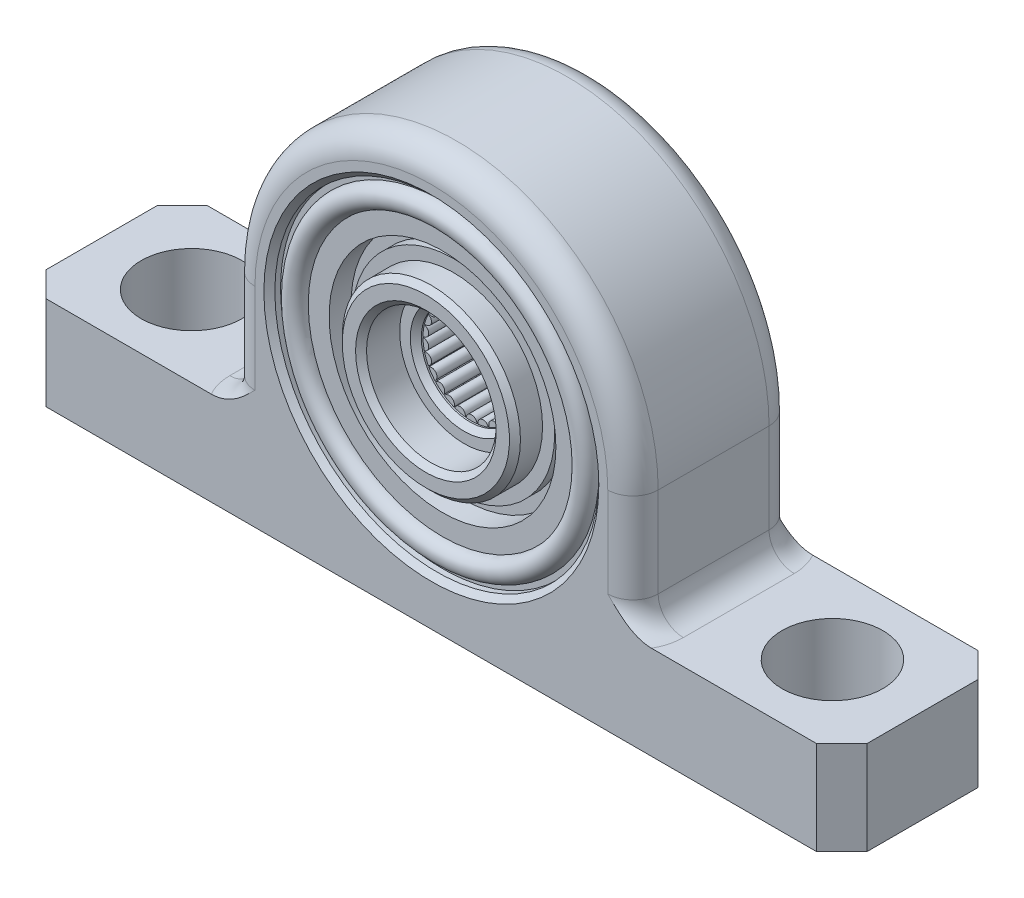
SolidWorks part; units mm, degrees
ref_plane "Front Plane" through (0, 0, 0) normal (0, 0, 1) x (1, 0, 0)
ref_plane "Top Plane" through (0, 0, 0) normal (0, 1, 0) x (1, 0, 0)
ref_plane "Right Plane" through (0, 0, 0) normal (1, 0, 0) x (0, 0, -1)
sketch "Sketch1" plane through (0, 0, 0) normal (0, 0, 1) x (1, 0, 0)
  line L0 (0, 14.25) -> (0, -14.25) construction
  line L1 (-28.5, -14.25) -> (28.5, -14.25) construction
  line L2 (-22.25, -14.25) -> (22.25, -14.25) construction
  line L3 (-28.5, -14.25) -> (-28.5, -7.75)
  line L4 (-28.5, -7.75) -> (-14, -7.75)
  line L5 (-14, 0.25) -> (-14, -7.75)
  line L6 (-15.75, -14.25) -> (-15.75, -7.75) construction
  circle A0 centre (-22.25, -14.25) radius 3.5
  circle A1 centre (22.25, -14.25) radius 3.5
  circle A2 centre (0, 0.25) radius 3
  circle A3 centre (0, 0.25) radius 14
  circle A4 centre (-22.25, -14.25) radius 6.5
  circle A5 centre (0, 0.25) radius 11.25
  circle A6 centre (0, 0.25) radius 4.5
  circle A7 centre (0, 0.25) radius 3.375 construction
  point P5 (0, -7.75)
  point P6 (0, 0.25)
  point P7 (-22.25, -14.25)
  point P8 (22.25, -14.25)
  point P22 (0, 3.25)
  point P23 (0, 11.5)
  point P25 (0, 9.5714)
  point P26 (0, 8.125)
  point P27 (0, 6.4375)
  point P28 (0, 4.75)
  dimension "Mounting Hole" = 7
  dimension "ID" = 6
  dimension "D4" = 9
  dimension "D9" = 6.75
  dimension "Height" = 28.5
  dimension "Length" = 57
  dimension "Lit G" = 6.5
  dimension "Center Height" = 14.5
  dimension "Mounting Center" = 44.5
  dimension "D1" = 1.75
  dimension "D2" = 11
  dimension "D3" = 8.25
  dimension "D5" = 6.75
  dimension "D6" = 1.9286
  dimension "D7" = 1.6875
  dimension "D8" = 1.6875
sketch "Sketch3" plane through (0, 0, 0) normal (0, 1, 0) x (1, 0, 0)
  line L0 (0, 5.6) -> (0, -5.6) construction
  point P2 (0, -6)
  point P4 (0, 4.5)
  dimension "CAD C" = 11.2
  dimension "Width" = 11.6
  dimension "D" = 10.5
sketch "Sketch6" plane through (0, 0, 0) normal (1, 0, 0) x (0, 0, -1)
  line L0 (-4.8262, 11.119) -> (-4.8262, 11.5)
  line L1 (-5.6, 11.5) -> (5.6, 11.5) construction
  line L2 (-5.6, 11.5) -> (-5.6, 0.25) construction
  line L3 (-5.6, 0.25) -> (5.6, 0.25) construction
  line L4 (5.6, 11.5) -> (5.6, 0.25) construction
  line L5 (-4.8262, 9.5714) -> (-4.8262, 8.125)
  line L6 (-3.3022, 8.125) -> (-4.8262, 8.125)
  line L7 (-4.0642, 7.2812) -> (-4.0642, 6.4375)
  line L8 (-4.0642, 6.4375) -> (-5.981, 6.4375)
  line L9 (-5.981, 6.4375) -> (-5.981, 4.75)
  line L10 (-4.0642, 7.2812) -> (-3.3022, 7.2812)
  line L11 (-3.3022, 7.2812) -> (-3.3022, 8.125)
  line L12 (-5.981, 4.75) -> (-3.3022, 4.75)
  line L13 (-3.3022, 4.75) -> (-3.3022, 3.25)
  line L14 (-3.3022, 3.25) -> (3.3022, 3.25)
  line L15 (-4.8262, 11.5) -> (4.8262, 11.5)
  line L16 (0, 0.25) -> (0, 32.5437) construction
  line L17 (0, 14.25) -> (0, -14.25) construction
  line L18 (0, 14.25) -> (0, -13.75) construction
  line L19 (3.3022, 4.75) -> (3.3022, 3.25)
  line L20 (5.981, 4.75) -> (3.3022, 4.75)
  line L21 (3.3022, 7.2812) -> (3.3022, 8.125)
  line L22 (4.0642, 7.2812) -> (3.3022, 7.2812)
  line L23 (5.981, 6.4375) -> (5.981, 4.75)
  line L24 (4.0642, 6.4375) -> (5.981, 6.4375)
  line L25 (4.0642, 7.2812) -> (4.0642, 6.4375)
  line L26 (3.3022, 8.125) -> (4.8262, 8.125)
  line L27 (4.8262, 9.5714) -> (4.8262, 8.125)
  line L28 (4.8262, 11.119) -> (4.8262, 11.5)
  arc A0 (-4.8262, 11.119) -> (-4.8262, 9.5714) centre (-4.8262, 10.3452) ccw
  arc A1 (4.8262, 11.119) -> (4.8262, 9.5714) centre (4.8262, 10.3452) cw
  point P40 (0, 11.5)
  point P41 (0, 3.25)
  dimension "D1" = 0.381
  dimension "D2" = 0.381
  dimension "D3" = 1.524
  dimension "D4" = 0.762
  dimension "D5" = 0.762
  dimension "D6" = 6.6044
revolve "Revolve1" add sketch "Sketch6" angle 360 about L3
sketch "Sketch7" plane through (0, 0, 0) normal (0, 0, 1) x (1, 0, 0)
  line L0 (0, 14.25) -> (0, -14.25) construction
  line L1 (-0.375, 3.625) -> (0, 0.25) construction
  line L2 (0, 0.25) -> (0.375, 3.625) construction
  circle A0 centre (0, 3.625) radius 0.375
  circle A1 centre (0, 0.25) radius 3.375 construction
  circle A2 centre (0, 0.25) radius 3 construction
  dimension "D1" = 0.75
  dimension "D2" = 12.68
sketch "Sketch8" plane through (0, 0, 3.3022) normal (0, 0, 1) x (1, 0, 0)
  circle A0 centre (0, 0.25) radius 3.375 construction
  circle A1 centre (0, 0.25) radius 3.375
extrude "Cut-Extrude2" cut sketch "Sketch8" against normal through all
sketch "Sketch9" plane through (0, 0, 0) normal (0, 0, 1) x (1, 0, 0)
  circle A0 centre (0, 3.625) radius 0.375 construction
  circle A1 centre (0, 3.625) radius 0.375
extrude "Boss-Extrude2" add sketch "Sketch9" along normal mid plane 5.6138
pattern_circular "CirPattern1" count 26 over 360 of "Boss-Extrude2"
chamfer "Chamfer2" distance 0.381 angle 45 6 edges at (4.5, 0.25, -5.981) (6.1875, 0.25, -5.981) (6.1875, 0.25, 5.981) (4.5, 0.25, 5.981) (3.375, 0.25, -3.3022) (3.375, 0.25, 3.3022)
sketch "Sketch4" plane through (0, 0, 0) normal (0, 0, 1) x (1, 0, 0)
  line L0 (-28.5, -14.25) -> (-28.5, -7.75) construction
  line L1 (-28.5, -7.75) -> (-14, -7.75) construction
  line L2 (-28.5, -14.25) -> (28.5, -14.25) construction
  line L3 (-28.5, -14.25) -> (-28.5, -7.75)
  line L4 (-28.5, -7.75) -> (-14, -7.75)
  line L5 (-28.5, -14.25) -> (28.5, -14.25)
  line L6 (-14, 0.25) -> (-14, -7.75) construction
  line L7 (-14, 0.25) -> (-14, -7.75)
  line L8 (0, 14.25) -> (0, -14.25) construction
  line L9 (14, 0.25) -> (14, -7.75)
  line L10 (28.5, -7.75) -> (14, -7.75)
  line L11 (28.5, -14.25) -> (28.5, -7.75)
  circle A0 centre (0, 0.25) radius 14 construction
  arc A1 (14, 0.25) -> (-14, 0.25) centre (0, 0.25) ccw
  circle A2 centre (0, 0.25) radius 11.25 construction
  circle A3 centre (0, 0.25) radius 11.25
extrude "Boss-Extrude1" add sketch "Sketch4" along normal up to vertex (5.6 mm away) and the other way up to vertex (5.6 mm away) up to point (0, 0, 5.6) other way up to point (0, 0, -5.6)
sketch "Sketch5" plane through (0, -7.75, 0) normal (0, 1, 0) x (1, 0, 0)
  circle A0 centre (-22.25, 0) radius 3.5
  circle A1 centre (22.25, 0) radius 3.5
  dimension "D1" = 7
extrude "Cut-Extrude1" cut sketch "Sketch5" against normal through all
chamfer "Chamfer1" distance 1.74 angle 45 4 edges at (28.5, -11, -5.6) (28.5, -11, 5.6) (-28.5, -11, 5.6) (-28.5, -11, -5.6)
fillet "Fillet1" radius 1.75 6 edges at (14, -3.75, -5.6) (0, 14.25, -5.6) (14, -3.75, 5.6) (0, 14.25, 5.6) (-14, -3.75, -5.6) (-14, -3.75, 5.6)
fillet "Fillet3" radius 1.75 6 edges at (-13.4874, -7.75, -5.0874) (-13.4874, -7.75, 5.0874) (-14, -7.75, 0) (13.4874, -7.75, -5.0874) (14, -7.75, 0) (13.4874, -7.75, 5.0874) tangent propagation no
chamfer "Chamfer3" distance 0.381 angle 45 2 edges at (11.25, 0.25, -5.6) (11.25, 0.25, 5.6)
equation "\"D1@Sketch5\"=\"Mounting Hole@Sketch1\""
equation "\"D1@Chamfer1\"=\"Width@Sketch3\"*.15"
equation "\"D1@Fillet1\"=\"D1@Sketch1\""
equation "\"D1@Fillet3\"=\"D1@Fillet1\""
equation "\"D3@Sketch1\"=\"D2@Sketch1\"*.750"
equation "\"D4@Sketch1\"=\"ID@Sketch1\"*1.5"
equation "\"D6@Sketch1\"=\"D5@Sketch1\"/3.5"
equation "\"D7@Sketch1\"=\"D5@Sketch1\"/4"
equation "\"D8@Sketch1\"=\"D5@Sketch1\"/4"
equation "\"D9@Sketch1\"=\"ID@Sketch1\"*1.125"
equation "\"D1@CirPattern1\"=(360/\"D2@Sketch7\")-2"
equation "\"D1@Boss-Extrude2\"=\"D6@Sketch6\"*.85"
